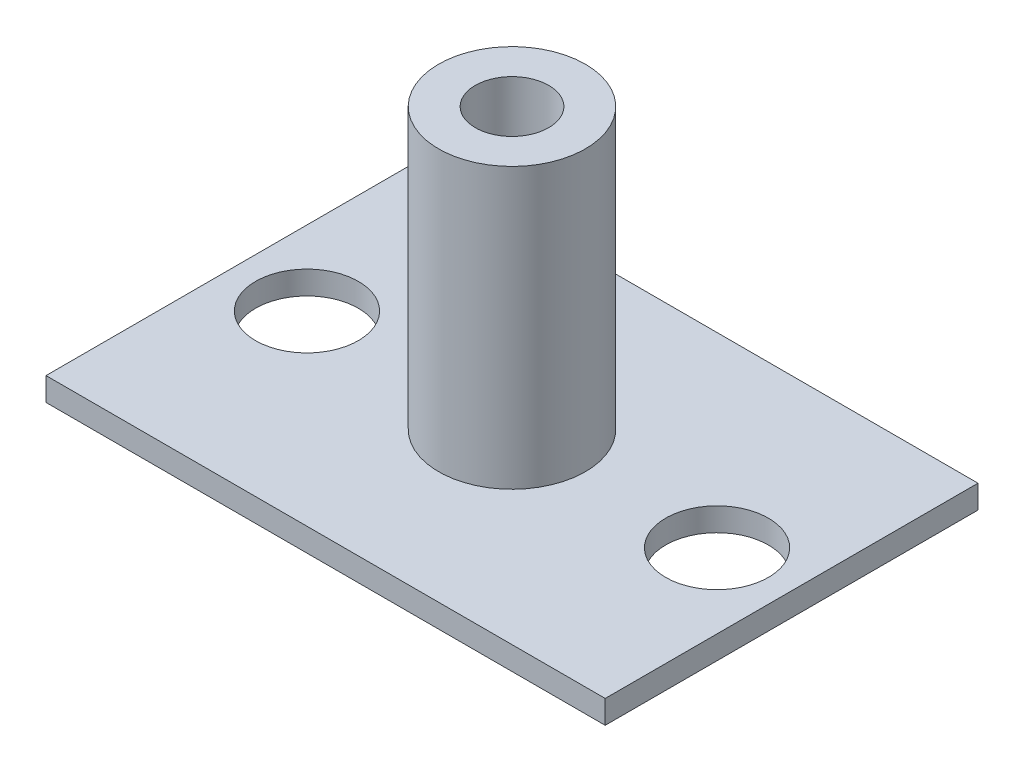
SolidWorks part; units mm, degrees
ref_plane "前视" through (0, 0, 0) normal (0, 0, 1) x (1, 0, 0)
ref_plane "上视" through (0, 0, 0) normal (0, 1, 0) x (1, 0, 0)
ref_plane "右视" through (0, 0, 0) normal (1, 0, 0) x (0, 0, -1)
sketch "Sketch1" plane through (0, 0, 0) normal (0, 1, 0) x (1, 0, 0)
  line L1 (-25.8417, 12.7) -> (12.2583, 12.7)
  line L2 (-25.8417, 12.7) -> (-25.8417, -12.7)
  line L3 (-25.8417, -12.7) -> (12.2583, -12.7)
  line L4 (12.2583, 12.7) -> (12.2583, -12.7)
  dimension "D1" = 25.4
  dimension "D2" = 38.1
extrude "Boss-Extrude1" add sketch "Sketch1" along normal blind 1.5875
ref_point "Point1"
sketch "Sketch3" plane through (0, 1.5875, 0) normal (0, 1, 0) x (1, 0, 0)
  circle A0 centre (-6.7917, 0) radius 5
  circle A1 centre (-6.7917, 0) radius 2.5
extrude "Boss-Extrude2" add sketch "Sketch3" along normal blind 19.05
ref_axis "Axis1" through (12.2583, 1.5875, 0) along (-1, 0, 0)
sketch "Sketch4" plane through (0, 1.5875, 0) normal (0, 1, 0) x (1, 0, 0)
  line L0 (12.2583, -12.7) -> (12.2583, 12.7) construction
  line L1 (-25.8417, 12.7) -> (-25.8417, -12.7) construction
  circle A0 centre (7.1783, 0) radius 3.5
  circle A1 centre (-20.7617, 0) radius 3.5
  point P0 (7.1783, 0)
  point P1 (12.2583, 0)
  point P4 (-20.7617, 0)
  dimension "D3" = 7
  dimension "D4" = 7
  dimension "D1" = 5.08
  dimension "D2" = 5.08
extrude "Cut-Extrude1" cut sketch "Sketch4" against normal through all
